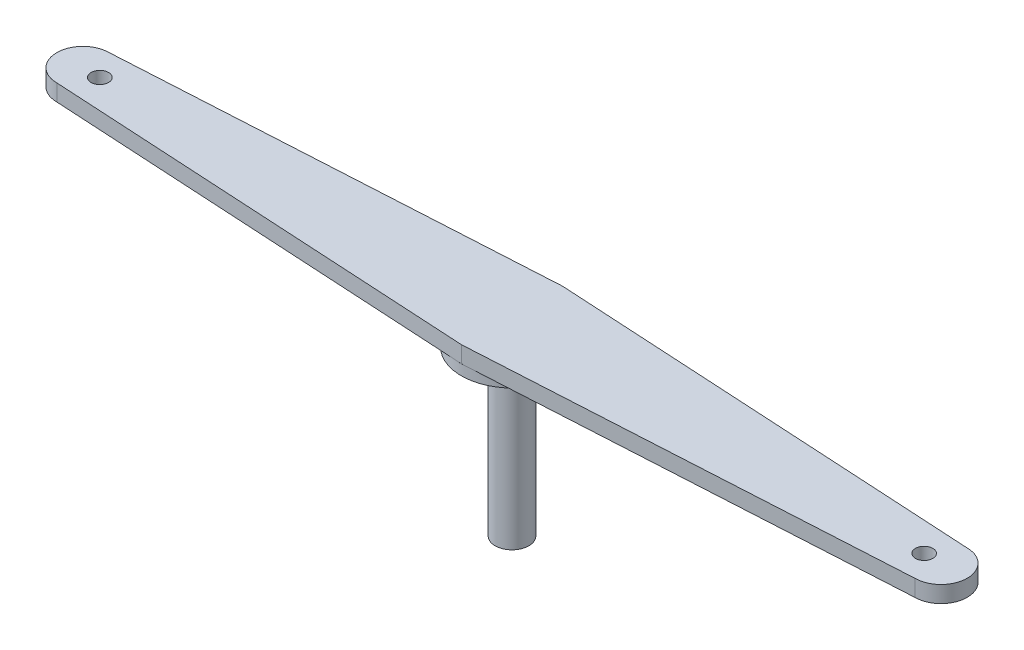
SolidWorks part; units mm, degrees
note: The reader was unsure of these and kept them because the rebuilt part matched: shared geometry of "Sketch1<4>".
ref_plane "Front Plane" through (0, 0, 0) normal (0, 0, 1) x (1, 0, 0)
ref_plane "Top Plane" through (0, 0, 0) normal (0, 1, 0) x (1, 0, 0)
ref_plane "Right Plane" through (0, 0, 0) normal (1, 0, 0) x (0, 0, -1)
sketch "Sketch1" plane through (0, 0, 0) normal (0, 1, 0) x (1, 0, 0)
  line L0 (-122.9, 0) -> (122.9, 0) construction
  line L1 (0, 14.5) -> (-122.9, 7.5)
  line L2 (0, 14.5) -> (122.9, 7.5)
  line L3 (122.9, -7.5) -> (0, -14.5)
  line L4 (0, -14.5) -> (-122.9, -7.5)
  circle A0 centre (0, 0) radius 4.75
  circle A1 centre (0, 0) radius 14.5
  arc A2 (-122.9, 7.5) -> (-122.9, -7.5) centre (-122.9, 0) ccw
  arc A3 (122.9, -7.5) -> (122.9, 7.5) centre (122.9, 0) ccw
  circle A4 centre (0, 0) radius 4.75
  point P6 (0, 0)
  dimension "D1" = 9.5
  dimension "D3" = 29
  dimension "D4" = 15
  dimension "D2" = 245.8
extrude "Boss-Extrude1" add sketch "Sketch1" along normal blind 4.75
extrude "Boss-Extrude2" add sketch "Sketch1<4>" against normal blind 50 contours A0
sketch "Sketch1<4>" plane through (0, 0, 0) normal (0, 1, 0) x (1, 0, 0) same geometry as "Sketch1"
sketch "Sketch3" plane through (0, 0, 0) normal (0, -1, 0) x (1, 0, 0)
  circle A0 centre (0, 0) radius 14.5
extrude "Boss-Extrude3" add sketch "Sketch3" along normal blind 3
sketch "Sketch4" plane through (0, 4.75, 0) normal (0, 1, 0) x (1, 0, 0)
  line L0 (111.7788, -80.7353) -> (111.7788, 0) construction
  line L1 (-122.9, 0) -> (122.9, 0) construction
  line L2 (-118.0597, -80.6846) -> (-118.0597, 0) construction
  circle A0 centre (111.7788, 0) radius 2.5
  circle A1 centre (-118.0597, 0) radius 2.5
  dimension "D1" = 5
  dimension "D2" = 5
extrude "Cut-Extrude1" cut sketch "Sketch4" against normal up to next
sketch "Sketch5" plane through (0, 4.75, 0) normal (0, 1, 0) x (1, 0, 0)
  line L0 (0, 0) -> (0, 13.3398) construction
  circle A0 centre (-118.0597, 0) radius 2.5
  circle A1 centre (118.0597, 0) radius 2.5
extrude "Cut-Extrude2" cut sketch "Sketch5" against normal blind 5
sketch "Sketch6" plane through (0, 4.75, 0) normal (0, 1, 0) x (1, 0, 0)
  circle A0 centre (111.7788, 0) radius 2.5
extrude "Boss-Extrude5" add sketch "Sketch6" against normal blind 5
sketch "Sketch7" plane through (0, -50, 0) normal (0, -1, 0) x (-1, 0, 0)
  circle A0 centre (0, 0) radius 4.825
  dimension "D1" = 9.65
extrude "Boss-Extrude6" add sketch "Sketch7" against normal up to next contours A0
sketch "Sketch8" plane through (0, -50, 0) normal (0, -1, 0) x (1, 0, 0)
  circle A0 centre (0, 0) radius 2
  dimension "D1" = 4
extrude "Cut-Extrude3" cut sketch "Sketch8" against normal blind 3
